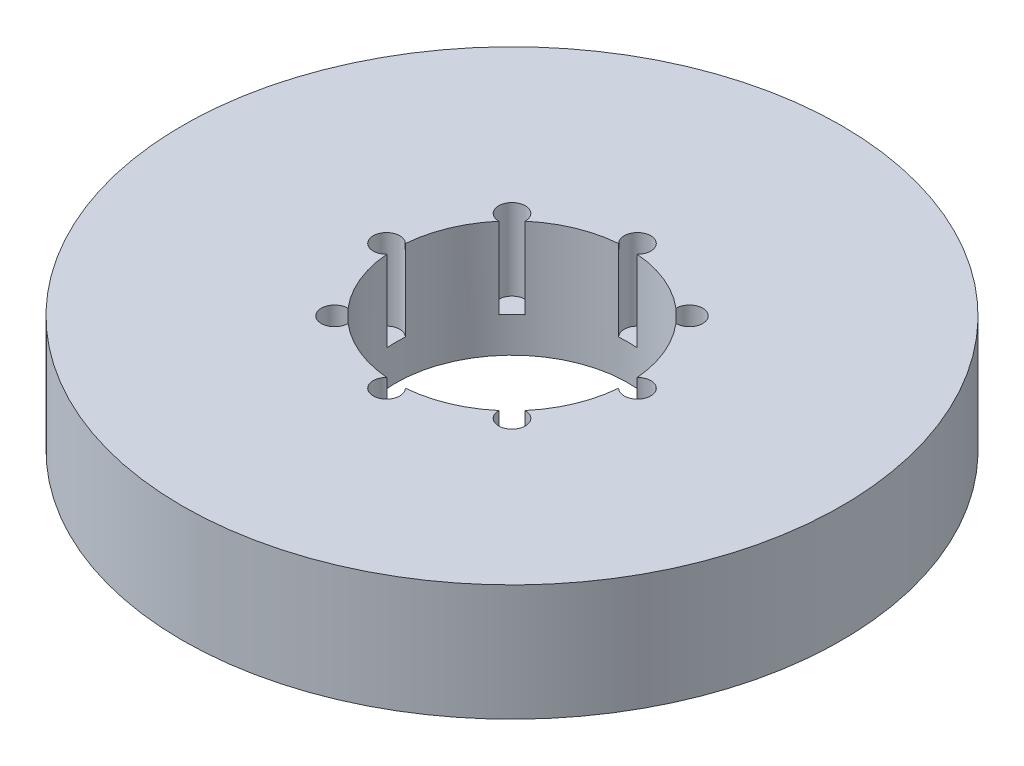
SolidWorks part; units mm, degrees
ref_plane "Front Plane" through (0, 0, 0) normal (0, 0, 1) x (1, 0, 0)
ref_plane "Top Plane" through (0, 0, 0) normal (0, 1, 0) x (1, 0, 0)
ref_plane "Right Plane" through (0, 0, 0) normal (1, 0, 0) x (0, 0, -1)
sketch "Sketch1" plane through (0, 0, 0) normal (0, 1, 0) x (1, 0, 0)
  circle A0 centre (0, 0) radius 85
  dimension "FLANGE_OD" = 170
extrude "Boss-Extrude1" add sketch "Sketch1" along normal blind 30
sketch "Sketch2" plane through (0, 0, 0) normal (0, 1, 0) x (1, 0, 0)
  circle A0 centre (0, 0) radius 30
  dimension "BORE_D" = 60
extrude "Cut-Extrude1" cut sketch "Sketch2" along normal through all
sketch "Sketch3" plane through (0, 30, 0) normal (0, 1, 0) x (1, 0, 0)
  circle A0 centre (0, 0) radius 32.3645 construction
  circle A1 centre (-32.3645, 0) radius 3.4315
  dimension "BOLT_D" = 6.8629
  dimension "BOLT_PCD" = 64.7291
extrude "Cut-Extrude2" cut sketch "Sketch3" against normal blind 20.9064
pattern_circular "CirPattern1" count 8 over 360 about axis through (0, 0, 0) along (0, 1, 0) of "Cut-Extrude2"
